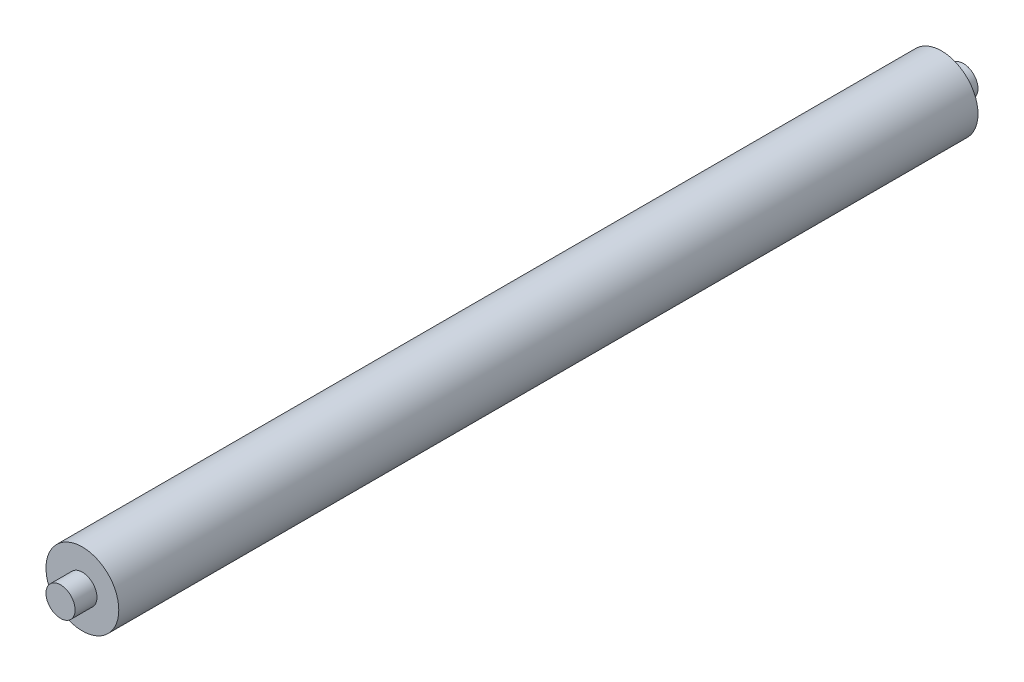
SolidWorks part; units mm, degrees
ref_plane "Front Plane" through (0, 0, 0) normal (0, 0, 1) x (1, 0, 0)
ref_plane "Top Plane" through (0, 0, 0) normal (0, 1, 0) x (1, 0, 0)
ref_plane "Right Plane" through (0, 0, 0) normal (1, 0, 0) x (0, 0, -1)
sketch "Sketch2" plane through (0, 0, 0) normal (0, 0, 1) x (1, 0, 0)
  circle A0 centre (0, 0) radius 25
  circle A1 centre (0, 0) radius 10
  dimension "D1" = 50
  dimension "D2" = 20
extrude "Boss-Extrude1" add sketch "Sketch2" along normal mid plane 590 contours A0 A1 | A1 | A1 | A0 region at (-24.2929, 0, 0) region at (0, 0, 0)
extrude "Boss-Extrude2" add sketch "Sketch2<3>" along normal blind 310 and the other way blind 310 contours A1 region at (0, 0, 0)
sketch "Sketch2<3>" plane through (0, 0, 0) normal (0, 0, 1) x (1, 0, 0) same geometry as "Sketch2"
